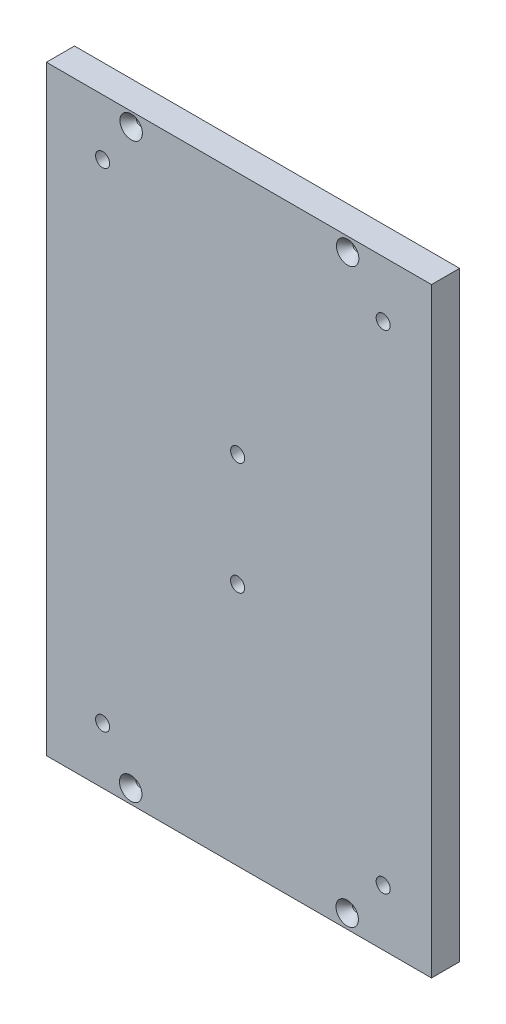
SolidWorks part; units mm, degrees
material "Beech"
ref_plane "Front Plane" through (0, 0, 0) normal (0, 0, 1) x (1, 0, 0)
ref_plane "Top Plane" through (0, 0, 0) normal (0, 1, 0) x (1, 0, 0)
ref_plane "Right Plane" through (0, 0, 0) normal (1, 0, 0) x (0, 0, -1)
sketch "Sketch1" plane through (0, 0, 0) normal (0, 0, 1) x (1, 0, 0)
  line L2 (125.2425, 0) -> (299.2638, 0)
  line L3 (125.2425, 0) -> (125.2425, 271.3655)
  line L4 (125.2425, 135.6828) -> (299.2638, 135.6828) construction
  line L5 (299.2638, 0) -> (299.2638, 271.3655)
  line L8 (125.2425, 271.3655) -> (299.2638, 271.3655)
  line L9 (299.2638, 0) -> (299.2638, 271.3655) construction
  point P15 (299.2638, 135.6828)
  point P16 (299.2638, 135.6828)
extrude "Boss-Extrude1" add sketch "Sketch1" along normal blind 12.7
hole_wizard "1/4 (0.25) Diameter Hole1" positions "Sketch2" profile "Sketch3" hole size "1/4" standard "ANSI Inch" end condition through all
sketch "Sketch2" plane through (0, 0, 0) normal (0, 0, -1) x (-1, 0, 0)
  point P0 (-277.4266, 245.9655)
  point P3 (-211.6533, 161.0828)
  point P6 (-150.6425, 245.9655)
  point P9 (-211.6533, 110.2828)
  point P12 (-277.4266, 25.4)
  point P15 (-150.6425, 25.4)
sketch "Sketch3" plane through (277.4266, 245.9655, 0) normal (1, 0, 0) x (0, 1, 0)
  line L0 (0, 0) -> (0, 12.7)
  line L1 (0, 12.7) -> (3.175, 12.7)
  line L2 (3.175, 12.7) -> (3.175, 0)
  line L5 (3.175, 0) -> (0, 0)
  line L11 (0, -6.35) -> (0, 107.95) construction
  dimension "Thru Hole Dia." = 6.35
  dimension "Thru Hole Depth" = 12.7
hole_wizard "Hole1" positions "Sketch4" profile "Sketch5" legacy
sketch "Sketch4" plane through (-494.9838, 135.8167, 12.7) normal (0, 0, 1) x (0, -1, 0)
  line L0 (129.4667, 794.2476) -> (129.4667, 620.2263) construction
  line L5 (0.134, 794.2476) -> (0, 620.4735) construction
  point P10 (129.4667, 658.3263)
  point P12 (129.4667, 756.1476)
  point P20 (-129.4082, 658.5259)
  point P21 (-129.2574, 756.3471)
sketch "Sketch5" plane through (261.3633, 265.0741, 12.7) normal (1, 0, 0) x (0, -1, 0)
  line L0 (0, 0) -> (0, 32.7039)
  line L1 (0, 32.7039) -> (1.5875, 31.75)
  line L2 (1.5875, 31.75) -> (1.5875, 4.0177)
  line L3 (1.5875, 4.0177) -> (5.08, 0)
  line L4 (5.08, 0) -> (0, 0)
  line L5 (0, -14.3089) -> (0, 102.4216) construction
  line L6 (0, 32.7039) -> (-1.5875, 31.75) construction
  line L7 (-1.5875, 4.0177) -> (-5.08, 0) construction
  dimension "Diameter" = 3.175
  dimension "Depth" = 31.75
  dimension "C-Sink Diameter" = 10.16
  dimension "C-Sink Angle" = 82
  dimension "Drill Angle" = 118
